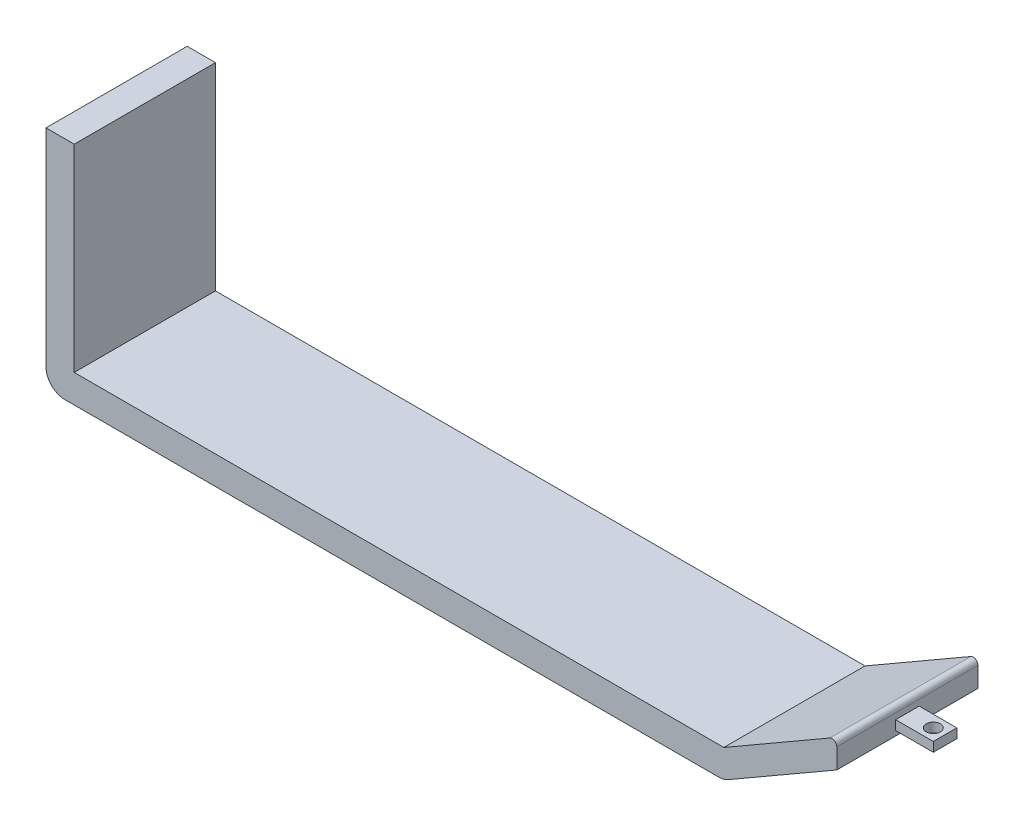
SolidWorks part; units mm, degrees
ref_plane "Front Plane" through (0, 0, 0) normal (0, 0, 1) x (1, 0, 0)
ref_plane "Top Plane" through (0, 0, 0) normal (0, 1, 0) x (1, 0, 0)
ref_plane "Right Plane" through (0, 0, 0) normal (1, 0, 0) x (0, 0, -1)
sketch "Sketch1" plane through (0, 0, 0) normal (0, 0, 1) x (1, 0, 0)
  line L1 (0, 0) -> (6.2204, 0)
  line L2 (0, 0) -> (0, 609.6)
  line L3 (0, 609.6) -> (76.2, 609.6)
  line L4 (76.2, 76.2) -> (76.2, 609.6)
  line L5 (0, 0) -> (1828.8, 0)
  line L6 (0, 0) -> (0, 7.7755)
  line L7 (76.2, 76.2) -> (1828.8, 76.2)
  line L9 (1828.8, 0) -> (2133.6, 175.9764)
  line L10 (1828.8, 76.2) -> (2133.6, 252.1764)
  line L11 (2133.6, 175.9764) -> (2133.6, 252.1764)
  dimension "D1" = 609.6
  dimension "D2" = 1828.8
  dimension "D3" = 76.2
  dimension "D4" = 76.2
  dimension "D5" = 30
extrude "Boss-Extrude1" add sketch "Sketch1" along normal blind 381 contours L5 L7 L4 L3 L2 L1 region at (22.1898, 3.8878, 0)
sketch "Sketch5" plane through (0, 0, 0) normal (-1, 0, 0) x (0, 0, 1)
  line L0 (0, 0) -> (381, 0) construction
  line L1 (158.75, 50.8) -> (222.25, 50.8)
  line L2 (158.75, 50.8) -> (158.75, 76.2)
  line L3 (158.75, 76.2) -> (222.25, 76.2)
  line L4 (222.25, 50.8) -> (222.25, 76.2)
  point P8 (190.5, 50.8)
  point P9 (190.5, 0)
  dimension "D1" = 63.5
  dimension "D2" = 25.4
  dimension "D3" = 0
  dimension "D4" = 50.8
extrude "Boss-Extrude4" add sketch "Sketch5" along normal blind 101.6
sketch "Sketch6" plane through (0, 76.2, 0) normal (0, 1, 0) x (1, 0, 0)
  line L0 (-101.6, -222.25) -> (-101.6, -158.75) construction
  line L1 (-101.6, -222.25) -> (0, -222.25) construction
  circle A0 centre (-63.5, -190.5) radius 19.05
  dimension "D1" = 38.1
  dimension "D2" = 38.1
  dimension "D3" = 31.75
extrude "Cut-Extrude3" cut sketch "Sketch6" against normal up to surface (25.4 mm away) up to face at (-50.8, 50.8, 190.5)
fillet "Fillet3" radius 50.8 1 edges at (1828.8, 0, 190.5)
fillet "Fillet4" radius 12.7 1 edges at (2133.6, 252.1764, 190.5)
fillet "Fillet5" radius 50.8 1 edges at (0, 0, 190.5)
sketch "Sketch7" plane through (2133.6, 0, 0) normal (1, 0, 0) x (0, 0, -1)
  line L0 (-381, 175.9764) -> (0, 175.9764) construction
  line L1 (-222.25, 188.6764) -> (-158.75, 188.6764)
  line L2 (-222.25, 188.6764) -> (-222.25, 214.0764)
  line L3 (-222.25, 214.0764) -> (-158.75, 214.0764)
  line L4 (-158.75, 188.6764) -> (-158.75, 214.0764)
  line L5 (-381, 175.9764) -> (0, 175.9764) construction
  point P10 (-190.5, 188.6764)
  point P11 (-190.5, 175.9764)
  dimension "D1" = 63.5
  dimension "D2" = 12.7
  dimension "D3" = 25.4
  dimension "D4" = 0
extrude "Boss-Extrude5" add sketch "Sketch7" along normal blind 101.6
sketch "Sketch8" plane through (0, 214.0764, 0) normal (0, 1, 0) x (1, 0, 0)
  line L0 (2235.2, -158.75) -> (2133.6, -158.75) construction
  line L1 (2235.2, -158.75) -> (2235.2, -222.25) construction
  circle A0 centre (2203.45, -190.5) radius 19.05
  point P4 (0, 0)
  point P7 (0, 0)
  dimension "D1" = 38.1
  dimension "D2" = 31.75
  dimension "D3" = 31.75
extrude "Cut-Extrude4" cut sketch "Sketch8" against normal up to surface (25.4 mm away) up to face at (2184.4, 188.6764, 190.5)
